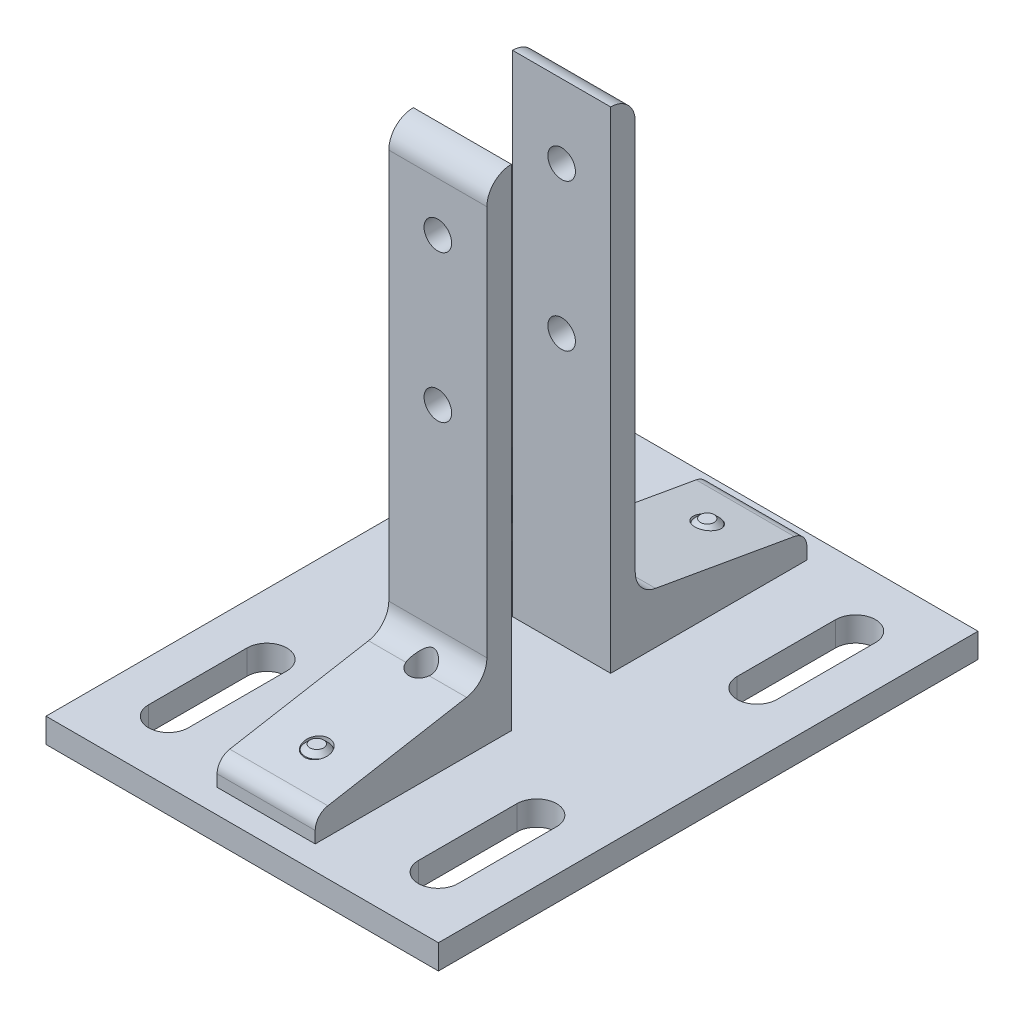
SolidWorks part; units mm, degrees
ref_plane "Front Plane" through (0, 0, 0) normal (0, 0, 1) x (1, 0, 0)
ref_plane "Top Plane" through (0, 0, 0) normal (0, 1, 0) x (1, 0, 0)
ref_plane "Right Plane" through (0, 0, 0) normal (1, 0, 0) x (0, 0, -1)
sketch "Sketch1" plane through (0, 0, 0) normal (0, 1, 0) x (1, 0, 0)
  line L0 (-34.925, 28.5242) -> (-34.925, 54.0258) construction
  line L1 (-50.8, -69.85) -> (50.8, -69.85)
  line L2 (-50.8, -69.85) -> (-50.8, 69.85)
  line L3 (-50.8, 69.85) -> (50.8, 69.85)
  line L4 (50.8, -69.85) -> (50.8, 69.85)
  line L5 (-50.8, -69.85) -> (50.8, 69.85) construction
  line L6 (-50.8, 69.85) -> (50.8, -69.85) construction
  line L7 (-40.0812, 28.5242) -> (-40.0812, 54.0258)
  line L8 (-29.7688, 28.5242) -> (-29.7688, 54.0258)
  line L9 (-34.925, -54.0258) -> (-34.925, -28.5242) construction
  line L10 (-40.0812, -54.0258) -> (-40.0812, -28.5242)
  line L11 (-29.7688, -54.0258) -> (-29.7688, -28.5242)
  line L12 (34.925, -54.0258) -> (34.925, -28.5242) construction
  line L13 (29.7688, -54.0258) -> (29.7688, -28.5242)
  line L14 (40.0812, -54.0258) -> (40.0812, -28.5242)
  line L15 (34.925, 28.5242) -> (34.925, 54.0258) construction
  line L16 (29.7688, 28.5242) -> (29.7688, 54.0258)
  line L17 (40.0812, 28.5242) -> (40.0812, 54.0258)
  line L18 (-50.8, 0) -> (50.8, 0) construction
  line L19 (-40.0812, 41.275) -> (-29.7688, 41.275) construction
  line L20 (40.0812, -41.275) -> (29.7688, -41.275) construction
  arc A0 (-40.0812, 28.5242) -> (-29.7688, 28.5242) centre (-34.925, 28.5242) ccw
  arc A1 (-29.7688, 54.0258) -> (-40.0812, 54.0258) centre (-34.925, 54.0258) ccw
  arc A2 (-40.0812, -54.0258) -> (-29.7688, -54.0258) centre (-34.925, -54.0258) ccw
  arc A3 (-29.7688, -28.5242) -> (-40.0812, -28.5242) centre (-34.925, -28.5242) ccw
  arc A4 (29.7688, -54.0258) -> (40.0812, -54.0258) centre (34.925, -54.0258) ccw
  arc A5 (40.0812, -28.5242) -> (29.7688, -28.5242) centre (34.925, -28.5242) ccw
  arc A6 (29.7688, 28.5242) -> (40.0812, 28.5242) centre (34.925, 28.5242) ccw
  arc A7 (40.0812, 54.0258) -> (29.7688, 54.0258) centre (34.925, 54.0258) ccw
  circle A8 centre (0, 50.546) radius 3.175 construction
  circle A9 centre (0, 23.495) radius 3.175 construction
  circle A10 centre (0, 50.546) radius 6.7437 construction
  circle A11 centre (0, 23.495) radius 6.7437 construction
  circle A12 centre (0, -23.495) radius 6.7437 construction
  circle A13 centre (0, -50.546) radius 6.7437 construction
  circle A14 centre (0, -23.495) radius 3.175 construction
  circle A15 centre (0, -50.546) radius 3.175 construction
  point P0 (0, 0)
  point P8 (-34.925, 41.275)
  point P14 (-34.925, -41.275)
  point P21 (34.925, -41.275)
  point P28 (34.925, 41.275)
  point P41 (0, 0)
  dimension "Attachment Hole Dia" = 6.35
  dimension "Attachment Counterbore" = 13.4874
  dimension "Base Length" = 101.6
  dimension "Base Width" = 139.7
  dimension "Slot Long Axis" = 35.814
  dimension "Slot Short Axis" = 10.3124
  dimension "Base Slot Width Offset" = 41.275
  dimension "Base Slot Length Offset" = 34.925
  dimension "D5" = 41.275
  dimension "D6" = 34.925
  dimension "Attachment Hole to Hole" = 27.051
  dimension "Attachment Hole Offset" = 23.495
sketch "Sketch2" plane through (0, 0, 0) normal (1, 0, 0) x (0, 0, -1)
  line L0 (63.6524, 0) -> (63.6524, 3.0226)
  line L1 (-69.85, 0) -> (69.85, 0) construction
  line L2 (-69.85, 0) -> (69.85, 0) construction
  line L3 (60.3781, 6.9248) -> (19.2024, 14.1852)
  line L4 (19.2024, 14.1852) -> (19.2024, 127)
  line L5 (19.2024, 127) -> (12.8524, 127)
  line L6 (12.8524, 127) -> (12.8524, 0)
  line L7 (12.8524, 0) -> (63.6524, 0)
  line L8 (0, 0) -> (0, 50000) construction
  line L9 (-12.8524, 0) -> (-63.6524, 0)
  line L10 (-12.8524, 127) -> (-12.8524, 0)
  line L11 (-19.2024, 127) -> (-12.8524, 127)
  line L12 (-19.2024, 14.1852) -> (-19.2024, 127)
  line L13 (-60.3781, 6.9248) -> (-19.2024, 14.1852)
  line L14 (-63.6524, 0) -> (-63.6524, 3.0226)
  arc A0 (63.6524, 3.0226) -> (60.3781, 6.9248) centre (59.69, 3.0226) ccw
  arc A1 (-63.6524, 3.0226) -> (-60.3781, 6.9248) centre (-59.69, 3.0226) cw
  dimension "Foot Bottom Radius" = 3.9624
  dimension "D1" = 10
  dimension "Foot Height" = 127
  dimension "Foot Width" = 50.8
  dimension "Foot Offset" = 12.8524
  dimension "Foot Flat" = 3.0226
  dimension "Foot Thickness" = 6.35
extrude "Boss-Extrude1" add sketch "Sketch1" against normal blind 6.35
extrude "Boss-Extrude2" add sketch "Sketch2" along normal mid plane 25.4
fillet "Fillet1" radius 6.35 4 edges at (0, 14.1852, 19.2024) (0, 127, 19.2024) (0, 14.1852, -19.2024) (0, 127, -19.2024)
sketch "Sketch3" plane through (0, -6.35, 0) normal (0, -1, 0) x (1, 0, 0)
  circle A0 centre (0, 50.546) radius 3.175 construction
  circle A1 centre (0, 23.495) radius 3.175 construction
  circle A2 centre (0, -23.495) radius 3.175 construction
  circle A3 centre (0, -50.546) radius 3.175 construction
  circle A4 centre (0, 50.546) radius 3.175
  circle A5 centre (0, 23.495) radius 3.175
  circle A6 centre (0, -23.495) radius 3.175
  circle A7 centre (0, -50.546) radius 3.175
extrude "Cut-Extrude1" cut sketch "Sketch3" against normal through all
sketch "Sketch4" plane through (0, -6.35, 0) normal (0, -1, 0) x (1, 0, 0)
  circle A0 centre (0, 50.546) radius 6.7437 construction
  circle A1 centre (0, 23.495) radius 6.7437 construction
  circle A2 centre (0, -23.495) radius 6.7437 construction
  circle A3 centre (0, -50.546) radius 6.7437 construction
  circle A4 centre (0, 50.546) radius 6.7437
  circle A5 centre (0, 23.495) radius 6.7437
  circle A6 centre (0, -23.495) radius 6.7437
  circle A7 centre (0, -50.546) radius 6.7437
extrude "Cut-Extrude2" cut sketch "Sketch4" against normal blind 3.175
sketch "Sketch5" plane through (0, -6.35, 0) normal (0, -1, 0) x (1, 0, 0)
  circle A5 centre (0, 50.546) radius 3.048
  circle A6 centre (0, 50.546) radius 3.048
  circle A8 centre (0, 23.495) radius 3.048
  circle A9 centre (0, 23.495) radius 3.048
  circle A11 centre (0, -23.495) radius 3.048
  circle A12 centre (0, -23.495) radius 3.048
  circle A14 centre (0, -50.546) radius 3.048
  circle A15 centre (0, -50.546) radius 3.048
  dimension "D1" = 0.127
  dimension "D2" = 0.127
  dimension "D3" = 0.127
  dimension "D4" = 0.127
extrude "Boss-Extrude4" add sketch "Sketch5" against normal blind 15.875 separate body
sketch "Sketch6" plane through (0, -6.35, 0) normal (0, -1, 0) x (1, 0, 0)
  circle A1 centre (0, 23.495) radius 6.6167
  circle A2 centre (0, 50.546) radius 6.6167
  circle A3 centre (0, 50.546) radius 6.6167
  circle A4 centre (0, -23.495) radius 6.6167
  circle A5 centre (0, -50.546) radius 6.6167
  dimension "D1" = 0.127
extrude "Boss-Extrude5" add sketch "Sketch6" against normal up to surface (3.175 mm away) up to face at (0, -3.175, 43.8023)
sketch "Sketch7" plane through (0, -6.35, 0) normal (0, -1, 0) x (1, 0, 0)
  line L1 (0, 47.498) -> (2.6396, 49.022)
  line L2 (2.6396, 49.022) -> (2.6396, 52.07)
  line L3 (2.6396, 52.07) -> (0, 53.594)
  line L4 (0, 53.594) -> (-2.6396, 52.07)
  line L5 (-2.6396, 52.07) -> (-2.6396, 49.022)
  line L6 (-2.6396, 49.022) -> (0, 47.498)
  line L7 (0, 20.447) -> (2.6396, 21.971)
  line L8 (2.6396, 21.971) -> (2.6396, 25.019)
  line L9 (2.6396, 25.019) -> (0, 26.543)
  line L10 (0, 26.543) -> (-2.6396, 25.019)
  line L11 (-2.6396, 25.019) -> (-2.6396, 21.971)
  line L12 (-2.6396, 21.971) -> (0, 20.447)
  line L13 (0, -26.543) -> (2.6396, -25.019)
  line L14 (2.6396, -25.019) -> (2.6396, -21.971)
  line L15 (2.6396, -21.971) -> (0, -20.447)
  line L16 (0, -20.447) -> (-2.6396, -21.971)
  line L17 (-2.6396, -21.971) -> (-2.6396, -25.019)
  line L18 (-2.6396, -25.019) -> (0, -26.543)
  line L19 (0, -53.594) -> (2.6396, -52.07)
  line L20 (2.6396, -52.07) -> (2.6396, -49.022)
  line L21 (2.6396, -49.022) -> (0, -47.498)
  line L22 (0, -47.498) -> (-2.6396, -49.022)
  line L23 (-2.6396, -49.022) -> (-2.6396, -52.07)
  line L24 (-2.6396, -52.07) -> (0, -53.594)
  circle A0 centre (0, 50.546) radius 2.6396 construction
  circle A1 centre (0, 23.495) radius 2.6396 construction
  circle A2 centre (0, -23.495) radius 2.6396 construction
  circle A3 centre (0, -50.546) radius 2.6396 construction
  circle A4 centre (0, 50.546) radius 3.048 construction
extrude "Cut-Extrude3" cut sketch "Sketch7" against normal blind 2.54
sketch "Sketch8" plane through (0, 0, 0) normal (0, 0, 1) x (1, 0, 0)
  line L0 (0, 0) -> (0, 69.85) construction
  line L1 (0, 69.85) -> (0, 107.95) construction
  circle A0 centre (0, 69.85) radius 3.5687
  circle A1 centre (0, 107.95) radius 3.5687
  point P5 (3.5687, 107.95)
  dimension "Top Hole Dia" = 7.1374
  dimension "Top hole to hole" = 38.1
  dimension "Top Hole Offset" = 69.85
extrude "Cut-Extrude4" cut sketch "Sketch8" against normal through all both and the other way through all
chamfer "Chamfer1" distance 1.27 angle 45 4 edges at (0, 9.525, -26.543) (0, 9.525, -53.594) (0, 9.525, 20.447) (0, 9.525, 47.498)
ref_plane "Plane1" through (0, 0, -41.275) normal (0, 0, 1) x (1, 0, 0)
ref_plane "Plane2" through (0, 0, 41.275) normal (0, 0, 1) x (1, 0, 0)
ref_plane "Plane3" through (-34.925, 0, 0) normal (1, 0, 0) x (0, 0, -1)
ref_plane "Plane4" through (34.925, 0, 0) normal (1, 0, 0) x (0, 0, -1)
ref_axis "Center Axis 1" through (-34.925, 26.67, -41.275) along (0, -1, 0)
ref_axis "Center Axis 2" through (34.925, 26.67, 41.275) along (0, -1, 0)
ref_axis "Center Axis 3" through (0, 107.95, 12.8524) along (0, 0, 1)
ref_axis "Center Axis 4" through (0, 69.85, 12.8524) along (0, 0, 1)
ref_plane "Contact Plane 1" through (0, -6.35, 0) normal (0, -1, 0) x (-1, 0, 0)
equation "\"D5@Sketch1\" = \"Base Slot Width Offset@Sketch1\""
equation "\"D6@Sketch1\" = \"Base Slot Length Offset@Sketch1\""
equation "\"D1@Cut-Extrude2\"=\"Base Thickness@Boss-Extrude1\"/2"
